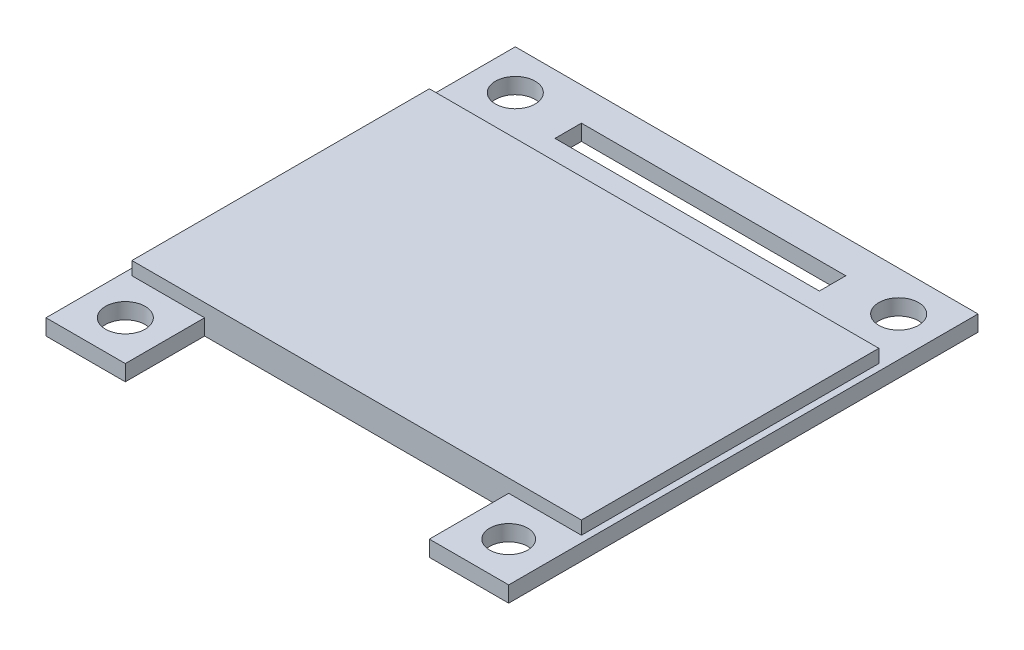
SolidWorks part; units mm, degrees
ref_plane "Front Plane" through (0, 0, 0) normal (0, 0, 1) x (1, 0, 0)
ref_plane "Top Plane" through (0, 0, 0) normal (0, 1, 0) x (1, 0, 0)
ref_plane "Right Plane" through (0, 0, 0) normal (1, 0, 0) x (0, 0, -1)
sketch "Sketch1" plane through (0, 0, 0) normal (0, 1, 0) x (1, 0, 0)
  line L1 (0, 0) -> (35, 0)
  line L2 (0, 0) -> (0, 29.5)
  line L3 (0, 29.5) -> (35, 29.5)
  line L4 (35, 0) -> (35, 29.5)
  line L9 (0, 0) -> (6, 0)
  line L10 (0, 0) -> (0, -6)
  line L11 (0, -6) -> (6, -6)
  line L12 (6, 0) -> (6, -6)
  line L13 (0.5, 22.5) -> (34.5, 22.5)
  line L14 (0.5, 22.5) -> (0.5, 0)
  line L15 (0.5, 0) -> (34.5, 0)
  line L16 (34.5, 22.5) -> (34.5, 0)
  line L21 (35, 0) -> (29, 0)
  line L22 (35, 0) -> (35, -6)
  line L23 (35, -6) -> (29, -6)
  line L24 (29, 0) -> (29, -6)
  line L25 (7.5, 27) -> (27.5, 27)
  line L26 (7.5, 27) -> (7.5, 25)
  line L27 (7.5, 25) -> (27.5, 25)
  line L28 (27.5, 27) -> (27.5, 25)
  circle A0 centre (3, -3) radius 1.5
  circle A4 centre (3, 26.5) radius 1.5
  circle A5 centre (32, 26.5) radius 1.5
  circle A6 centre (32, -3) radius 1.4397
  point P27 (27.5, 26)
  dimension "D11" = 29.5
  dimension "D14" = 3
  dimension "D1" = 35.5
  dimension "D2" = 35
  dimension "D3" = 6
  dimension "D4" = 6
  dimension "D5" = 6
  dimension "D6" = 6
  dimension "D7" = 0.5
  dimension "D8" = 0.5
  dimension "D9" = 0
  dimension "D10" = 7
  dimension "D12" = 3
  dimension "D13" = 3
  dimension "D15" = 3
  dimension "D16" = 29.5
  dimension "D17" = 3
  dimension "D18" = 3
  dimension "D19" = 3.5
  dimension "D20" = 2
  dimension "D21" = 20
  dimension "D22" = 7.5
extrude "Boss-Extrude3" add sketch "Sketch1" along normal blind 1.2 contours L15 L24 L23 L22 L1 A6 | L13 L16 L1 L4 L3 L2 L14 A5 A4 L25 L28 L27 L26 | L12 L9 L1 L10 L11 A0 region at (17.5, 0, -24.4114) region at (0.25, 0, 0.0849) region at (31.75, 0, 0.0849)
extrude "Boss-Extrude4" add sketch "Sketch1<7>" along normal blind 2.2 contours L16 L13 L14 L9 L1 L15 region at (17.5, 0, -11.25)
sketch "Sketch1<7>" plane through (0, 0, 0) normal (0, 1, 0) x (1, 0, 0) same geometry as "Sketch1"
